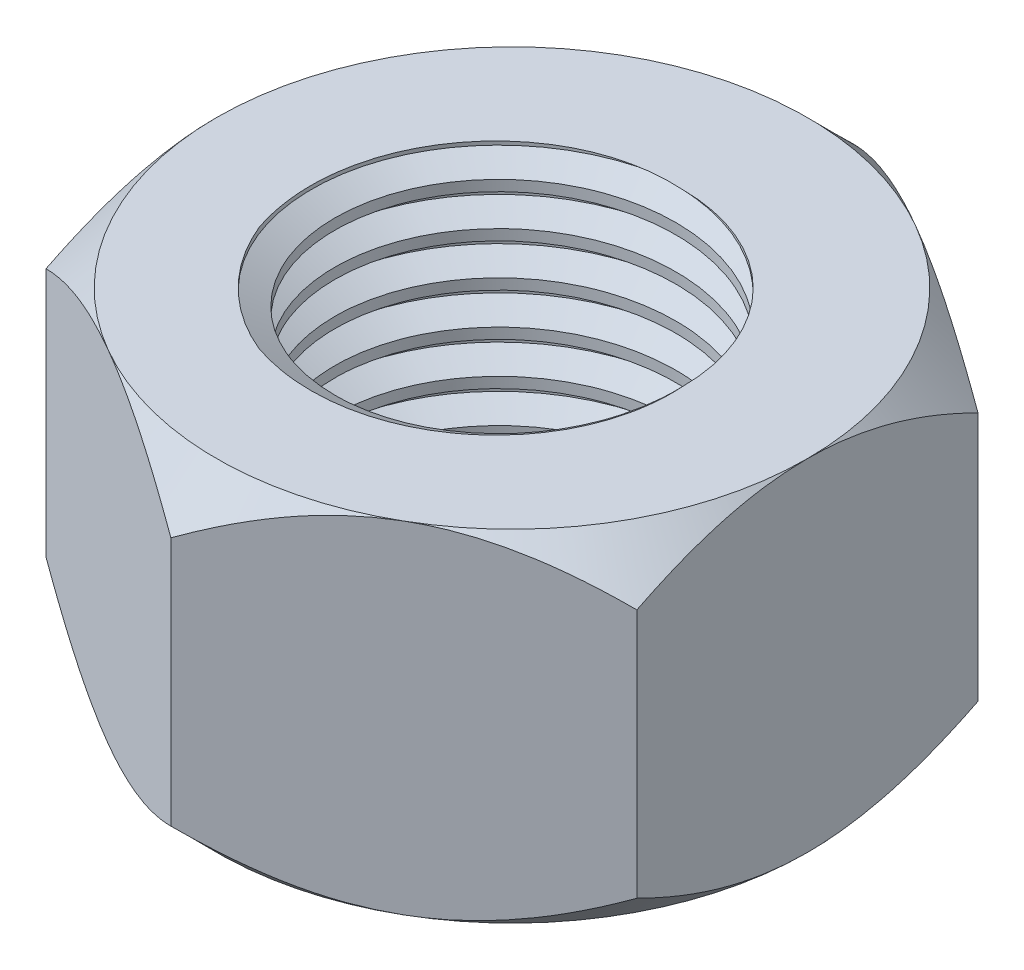
SolidWorks part; units mm, degrees
ref_plane "Front Plane" through (0, 0, 0) normal (0, 0, 1) x (1, 0, 0)
ref_plane "Top Plane" through (0, 0, 0) normal (0, 1, 0) x (1, 0, 0)
ref_plane "Right Plane" through (0, 0, 0) normal (1, 0, 0) x (0, 0, -1)
sketch "Sketch1" plane through (0, 0, 0) normal (0, 1, 0) x (1, 0, 0)
  line L1 (8.6603, -5) -> (8.6603, 5)
  line L2 (8.6603, 5) -> (0, 10)
  line L3 (0, 10) -> (-8.6603, 5)
  line L4 (-8.6603, 5) -> (-8.6603, -5)
  line L5 (-8.6603, -5) -> (0, -10)
  line L6 (0, -10) -> (8.6603, -5)
  circle A0 centre (0, 0) radius 8.6603 construction
  circle A1 centre (0, 0) radius 5
  dimension "D1" = 10
  dimension "D2" = 10
extrude "Boss-Extrude1" add sketch "Sketch1" along normal mid plane 10
sketch "Sketch3" plane through (0, -5, 0) normal (0, -1, 0) x (1, 0, 0)
  line L0 (-8.6603, 5) -> (0, 10) construction
  circle A1 centre (0, 0) radius 8.6603
extrude "Cut-Extrude2" cut sketch "Sketch3" against normal blind 10 draft 45 flip side to cut
mirror "Mirror1" about plane through (0, 0, 0) normal (0, 1, 0) of "Cut-Extrude2"
thread "Thread1" pitch 1.25 method cut profile "Thread Profile1" start angle 0, offset 0, length 10, pitch 1.25, diameter 10
ref_plane "Plane1" through (5, -5, 0) normal (0, 0, 1) x (1, 0, 0)
sketch "Thread Profile1" plane through (5, -5, 0) normal (0, 0, 1) x (1, 0, 0)
  line L0 (0, 0) -> (0, 1.25) construction
  line L1 (0, 0) -> (0.6766, 0.3906)
  line L2 (0.6766, 0.3906) -> (0.6766, 0.5469)
  line L3 (0.6766, 0.5469) -> (0, 0.9375)
  line L4 (0.6766, 0.4687) -> (0, 0.4687) construction
  line L11 (0, 0) -> (0, 0.9375)
  point P2 (0, 0)
  dimension "Pitch" = 1.25
  dimension "Profile_Angle" = 60
  dimension "Profile_Land" = 0.1562
  dimension "Profile_Height" = 0.6766
